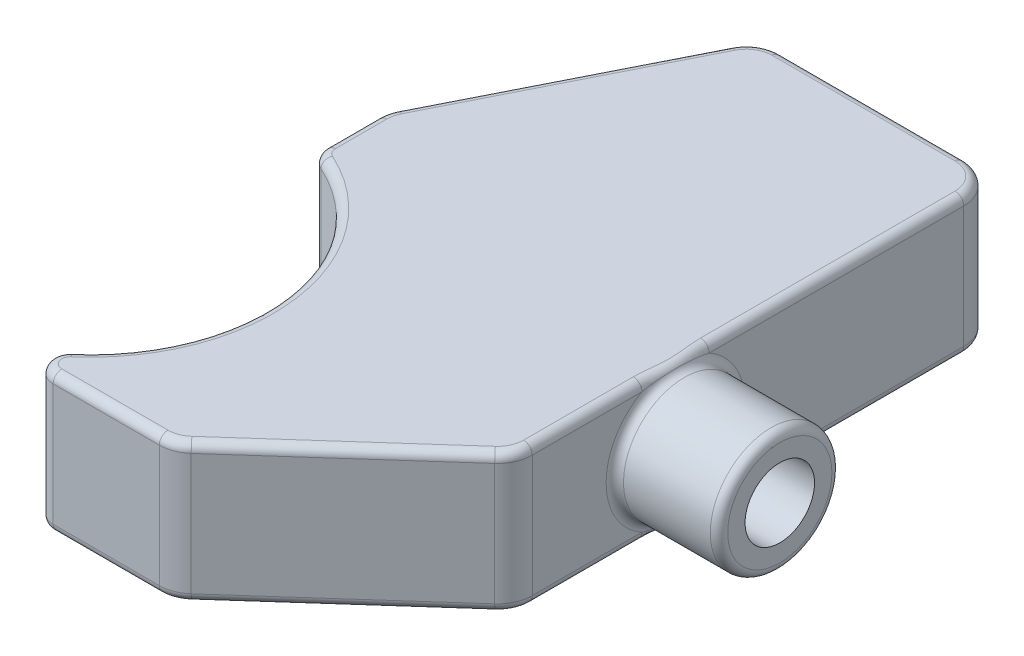
SolidWorks part; units mm, degrees
ref_plane "Front Plane" through (0, 0, 0) normal (0, 0, 1) x (1, 0, 0)
ref_plane "Top Plane" through (0, 0, 0) normal (0, 1, 0) x (1, 0, 0)
ref_plane "Right Plane" through (0, 0, 0) normal (1, 0, 0) x (0, 0, -1)
sketch "Sketch2" plane through (0, 0, 0) normal (0, 1, 0) x (1, 0, 0)
  line L0 (-52.9864, -9.8629) -> (-46.8752, -9.8629)
  line L1 (-45.5441, -9.3556) -> (-36.3065, -1.118)
  line L2 (-35.6377, 0.3747) -> (-35.6377, 25.2147)
  line L3 (-37.6377, 27.2147) -> (-48.1625, 27.2147)
  line L4 (-49.949, 26.1139) -> (-56.3747, 13.3471)
  line L5 (-56.5882, 12.4479) -> (-56.5882, 9.4847)
  arc A0 (-56.0036, 8.5751) -> (-53.6383, -8.1046) centre (-60.1572, -0.5215) cw
  arc A1 (-48.1625, 27.2147) -> (-49.949, 26.1139) centre (-48.1625, 25.2147) ccw
  arc A2 (-35.6377, 25.2147) -> (-37.6377, 27.2147) centre (-37.6377, 25.2147) ccw
  arc A3 (-36.3065, -1.118) -> (-35.6377, 0.3747) centre (-37.6377, 0.3747) ccw
  arc A4 (-46.8752, -9.8629) -> (-45.5441, -9.3556) centre (-46.8752, -7.8629) ccw
  arc A5 (-53.6383, -8.1046) -> (-52.9864, -9.8629) centre (-52.9864, -8.8629) ccw
  arc A6 (-56.5882, 9.4847) -> (-56.0036, 8.5751) centre (-55.5882, 9.4847) ccw
  arc A7 (-56.5882, 12.4479) -> (-56.3747, 13.3471) centre (-54.5882, 12.4479) cw
  dimension "D1" = 2
  dimension "D2" = 2
  dimension "D3" = 2
  dimension "D4" = 2
  dimension "D5" = 1
  dimension "D6" = 1
  dimension "D7" = 2
extrude "Boss-Extrude3" add sketch "Sketch2" along normal blind 8
sketch "Sketch5" plane through (-35.6377, 0, 0) normal (1, 0, 0) x (0, 0, -1)
  circle A0 centre (8.6255, 4) radius 3.5
extrude "Boss-Extrude4" add sketch "Sketch5" along normal blind 6
sketch "Sketch6" plane through (-29.6377, 0, 0) normal (1, 0, 0) x (0, 0, -1)
  line L1 (9.4677, 5.7946) -> (8.2521, 5.9469)
  line L2 (8.2521, 5.9469) -> (7.179, 5.3556)
  line L3 (7.179, 5.3556) -> (6.6585, 4.2465)
  line L4 (6.6585, 4.2465) -> (6.8893, 3.0432)
  line L5 (6.8893, 3.0432) -> (7.7832, 2.2054)
  line L6 (7.7832, 2.2054) -> (8.9989, 2.0531)
  line L7 (8.9989, 2.0531) -> (10.072, 2.6444)
  line L8 (10.072, 2.6444) -> (10.5925, 3.7535)
  line L9 (10.5925, 3.7535) -> (10.3617, 4.9568)
  line L10 (10.3617, 4.9568) -> (9.4677, 5.7946)
  circle A0 centre (8.6255, 4) radius 1.8854 construction
extrude "Cut-Extrude4" cut sketch "Sketch6" against normal blind 11
sketch "Sketch8" plane through (-29.6377, 0, 0) normal (1, 0, 0) x (0, 0, -1)
  circle A2 centre (8.6255, 4) radius 2
extrude "Cut-Extrude6" cut sketch "Sketch8" against normal blind 6
fillet "Fillet4" radius 0.5 1 edges at (-29.6377, 4, -12.1255)
fillet "Fillet5" radius 0.5 1 edges at (-35.6377, 4, -5.1255)
fillet "Fillet6" radius 0.5 15 edges at (-35.8125, 8, 0.4431) (-40.9253, 8, 5.2368) (-46.1629, 8, 9.7318) (-49.9308, 8, 9.8629) (-53.924, 8, 9.2106) (-50.2562, 8, -0.8825) (-56.4294, 8, -8.9441) (-56.5882, 8, -10.9663) (-56.5341, 8, -12.91) (-53.1618, 8, -19.7305) (-49.2117, 8, -26.9174) (-42.9001, 8, -27.2147) (-36.2235, 8, -26.6289) (-35.6377, 8, -16.9201) (-35.6377, 8, -4.5001)
fillet "Fillet7" radius 0.5 15 edges at (-35.8125, 0, 0.4431) (-40.9253, 0, 5.2368) (-46.1629, 0, 9.7318) (-49.9308, 0, 9.8629) (-53.924, 0, 9.2106) (-50.2562, 0, -0.8825) (-56.4294, 0, -8.9441) (-56.5882, 0, -10.9663) (-56.5341, 0, -12.91) (-53.1618, 0, -19.7305) (-49.2117, 0, -26.9174) (-42.9001, 0, -27.2147) (-36.2235, 0, -26.6289) (-35.6377, 0, -16.9201) (-35.6377, 0, -4.5001)
